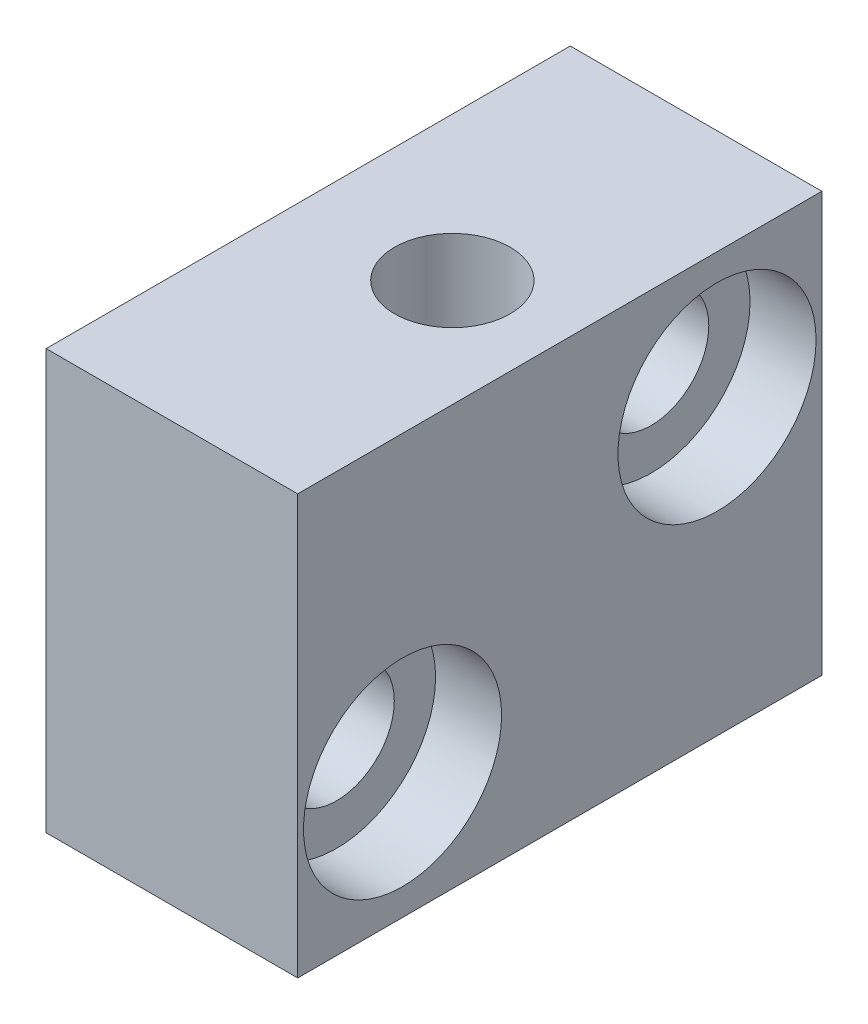
SolidWorks part; units mm, degrees
material "PET"
ref_plane "Front Plane" through (0, 0, 0) normal (1, 0, 0) x (0, 1, 0)
ref_plane "Top Plane" through (0, 0, 0) normal (0, 0, 1) x (0, 1, 0)
ref_plane "Right Plane" through (0, 0, 0) normal (0, 1, 0) x (-1, 0, 0)
sketch "Sketch1" plane through (0, 0, 0) normal (1, 0, 0) x (0, 1, 0)
  line L1 (6.35, -7.9375) -> (-6.35, -7.9375)
  line L2 (6.35, -7.9375) -> (6.35, 7.9375)
  line L3 (6.35, 7.9375) -> (-6.35, 7.9375)
  line L4 (-6.35, -7.9375) -> (-6.35, 7.9375)
  line L5 (6.35, -7.9375) -> (-6.35, 7.9375) construction
  line L6 (6.35, 7.9375) -> (-6.35, -7.9375) construction
  point P0 (0, 0)
  dimension "D1" = 15.875
  dimension "D2" = 12.7
extrude "Boss-Extrude1" add sketch "Sketch1" along normal blind 7.62
sketch "Sketch3" plane through (0, -6.35, 0) normal (0, -1, 0) x (1, 0, 0)
  line L10 (0, 7.9375) -> (0, -7.9375)
  line L11 (0, -7.9375) -> (7.62, -7.9375)
  line L12 (7.62, -7.9375) -> (7.62, 7.9375)
  line L13 (7.62, 7.9375) -> (0, 7.9375)
  line L14 (0, 7.9375) -> (0, -7.9375)
  line L15 (0, -7.9375) -> (7.62, -7.9375)
  line L16 (7.62, -7.9375) -> (7.62, 7.9375)
  line L17 (7.62, 7.9375) -> (0, 7.9375)
  circle A0 centre (4.3663, 0) radius 1.75
  circle A1 centre (4.3663, 0) radius 5 construction
  circle A2 centre (4.3663, 0) radius 3 construction
  point P2 (9.3663, 0)
  point P3 (2.6163, 0)
  point P6 (-6.35, 0)
  dimension "D1" = 3.5
  dimension "D2" = 10
  dimension "D6" = 6
  dimension "D3" = 15.7163
  dimension "D4" = 6.35
  dimension "D5" = 0
extrude "Cut-Extrude1" cut sketch "Sketch3" against normal blind 22.2885 contours A0 region at (4.3663, -6.35, 0)
sketch "Sketch4" plane through (7.62, 0, 0) normal (1, 0, 0) x (0, 1, 0)
  line L0 (-6.35, 7.9375) -> (-6.35, -7.9375) construction
  line L1 (2.54, -4.7625) -> (-2.54, -4.7625) construction
  line L2 (2.54, -4.7625) -> (2.54, 4.7625) construction
  line L3 (2.54, 4.7625) -> (-2.54, 4.7625) construction
  line L4 (-2.54, -4.7625) -> (-2.54, 4.7625) construction
  line L5 (2.54, -4.7625) -> (-2.54, 4.7625) construction
  line L6 (2.54, 4.7625) -> (-2.54, -4.7625) construction
  line L7 (6.35, 7.9375) -> (-6.35, 7.9375) construction
  circle A5 centre (-2.54, 4.7625) radius 1.75
  circle A6 centre (2.54, -4.7625) radius 1.75
  point P0 (0, 0)
  dimension "D3" = 3.5
  dimension "D1" = 3.81
  dimension "D2" = 3.175
extrude "Cut-Extrude2" cut sketch "Sketch4" against normal blind 22.2885 contours A5 | A6 region at (7.62, -2.54, 4.7625) region at (7.62, 2.54, -4.7625)
sketch "Sketch5" plane through (7.62, 0, 0) normal (1, 0, 0) x (0, 1, 0)
  circle A0 centre (2.54, -4.7625) radius 1.75 construction
  circle A1 centre (-2.54, 4.7625) radius 1.75 construction
  circle A2 centre (2.54, -4.7625) radius 1.75 construction
  circle A3 centre (-2.54, 4.7625) radius 1.75 construction
  circle A4 centre (-2.54, 4.7625) radius 3
  circle A5 centre (2.54, -4.7625) radius 3
  dimension "D1" = 6
extrude "Cut-Extrude3" cut sketch "Sketch5" against normal blind 2
